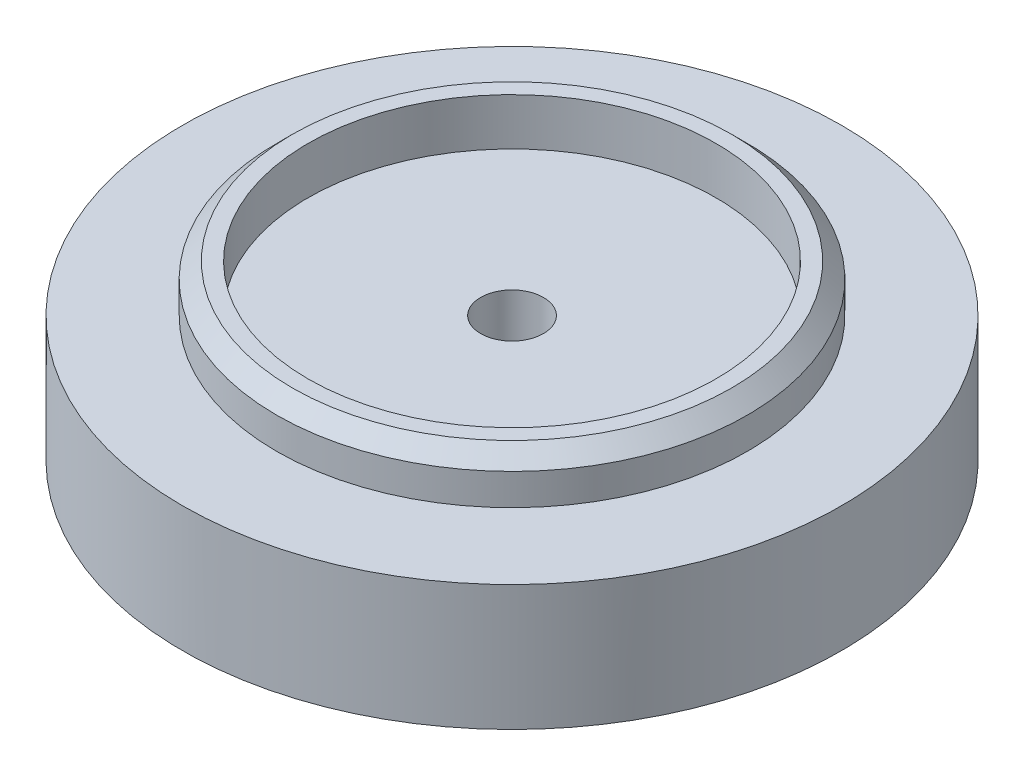
SolidWorks part; units mm, degrees
ref_plane "Płaszczyzna przednia" through (0, 0, 0) normal (0, 0, 1) x (1, 0, 0)
ref_plane "Płaszczyzna górna" through (0, 0, 0) normal (0, 1, 0) x (1, 0, 0)
ref_plane "Płaszczyzna prawa" through (0, 0, 0) normal (1, 0, 0) x (0, 0, -1)
sketch "Sketch1" plane through (0, 0, 0) normal (0, 1, 0) x (1, 0, 0)
  circle A0 centre (0, 0) radius 21
  circle A1 centre (0, 0) radius 2
  dimension "D1" = 42
  dimension "D2" = 4
extrude "Boss-Extrude1" add sketch "Sketch1" along normal blind 4
sketch "Sketch2" plane through (0, 4, 0) normal (0, 1, 0) x (1, 0, 0)
  circle A0 centre (0, 0) radius 15
  circle A1 centre (0, 0) radius 2 construction
  circle A2 centre (0, 0) radius 2
  circle A3 centre (0, 0) radius 13
  dimension "D1" = 30
  dimension "D2" = 2
extrude "Boss-Extrude2" add sketch "Sketch2" along normal blind 3 contours A0 A3 region at (-14.5757, 4, 0)
chamfer "Chamfer1" distance 1 angle 45 1 edges at (0, 7, 15)
sketch "Sketch3" plane through (0, 0, 0) normal (0, -1, 0) x (1, 0, 0)
  circle A0 centre (0, 0) radius 2.5
  circle A1 centre (0, 0) radius 21
  circle A2 centre (0, 0) radius 21
  dimension "D2" = 5
  dimension "D1" = 0
extrude "Boss-Extrude3" add sketch "Sketch3" along normal blind 4
sketch "Sketch4" plane through (0, 0, 0) normal (0, -1, 0) x (1, 0, 0)
  circle A0 centre (0, 0) radius 2.5 construction
  circle A1 centre (0, 0) radius 2 construction
  circle A2 centre (0, 0) radius 2.5
  circle A3 centre (0, 0) radius 2
extrude "Boss-Extrude4" add sketch "Sketch4" along normal blind 2
